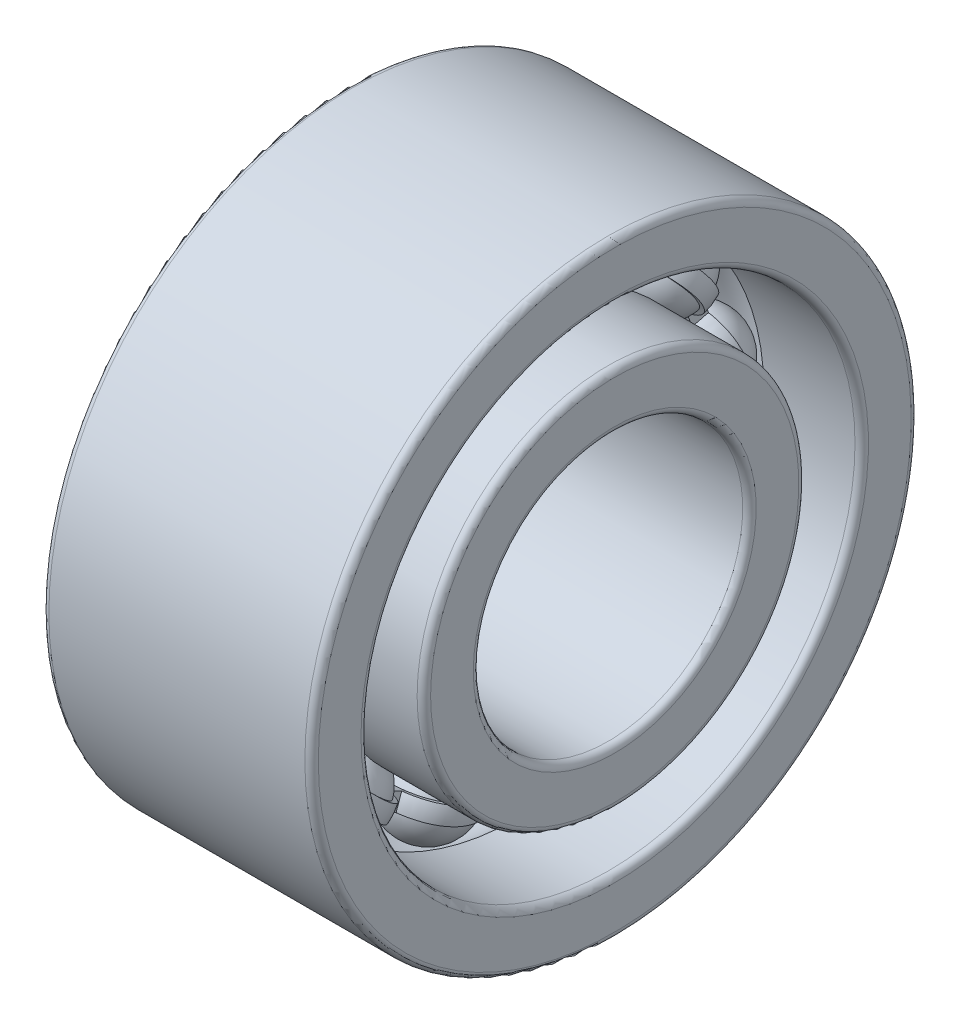
SolidWorks part; units mm, degrees
note: '?' marks a value the reader was unsure of.
material "AISI 304"
ref_plane "前视基准面" through (0, 0, 0) normal (0, 0, 1) x (1, 0, 0)
ref_plane "上视基准面" through (0, 0, 0) normal (0, 1, 0) x (1, 0, 0)
ref_plane "右视基准面" through (0, 0, 0) normal (1, 0, 0) x (0, 0, -1)
sketch "尺寸草图" plane through (0, 0, 0) normal (0, 0, 1) x (1, 0, 0)
  line L0 (-19.9271, 0) -> (19.9271, 0) construction
  line L1 (0, 21.603) -> (0, -21.603) construction
  line L2 (-1.9, 4.5) -> (1.9, 4.5)
  line L3 (2, 4.4) -> (2, 3.7667)
  line L4 (-2, 4.4) -> (-2, 3.7667)
  line L5 (-1.9, 3.6667) -> (1.9, 3.6667)
  line L6 (-3.5, 3.25) -> (3.3577, 3.25) construction
  line L7 (-1.9, 2.8333) -> (1.9, 2.8333)
  line L8 (2, 2.7333) -> (2, 2.1)
  line L9 (1.9, 2) -> (-1.9, 2)
  line L10 (-2, 2.1) -> (-2, 2.7333)
  line L11 (0, 3.25) -> (0, 3.875) construction
  circle A0 centre (0, 3.25) radius 0.625
  arc A1 (2, 3.7667) -> (1.9, 3.6667) centre (1.9, 3.7667) cw
  arc A2 (2, 2.7333) -> (1.9, 2.8333) centre (1.9, 2.7333) ccw
  arc A3 (-1.9, 2.8333) -> (-2, 2.7333) centre (-1.9, 2.7333) ccw
  arc A4 (-1.9, 3.6667) -> (-2, 3.7667) centre (-1.9, 3.7667) cw
  arc A5 (-1.9, 2) -> (-2, 2.1) centre (-1.9, 2.1) cw
  arc A6 (1.9, 2) -> (2, 2.1) centre (1.9, 2.1) ccw
  arc A7 (2, 4.4) -> (1.9, 4.5) centre (1.9, 4.4) ccw
  arc A8 (-1.9, 4.5) -> (-2, 4.4) centre (-1.9, 4.4) ccw
  point P7 (0, 0)
  point P25 (-2, 2.8333)
  point P28 (-2, 3.6667)
  point P31 (-2, 2)
  point P36 (2, 4.5)
  point P39 (-2, 4.5)
  dimension "D1" = 0.2083
  dimension "D3" = 0.1
  dimension "B" = 4
  dimension "D2" = 2
  dimension "D" = 9
  dimension "(d)" = 4
  dimension "D5" = 3.25
  dimension "D6" = 0.8333
  dimension "D7" = 0.8333
sketch "草图2" plane through (0, 0, 0) normal (0, 0, 1) x (1, 0, 0)
  line L6 (1.9, 2) -> (-1.9, 2) construction
  line L8 (-2, 4.4) -> (-2, 3.7667) construction
  line L9 (-1.9, 3.6667) -> (1.9, 3.6667) construction
  line L10 (-1.9, 4.5) -> (1.9, 4.5) construction
  line L11 (2, 4.4) -> (2, 3.7667) construction
  line L12 (2, 2.7333) -> (2, 2.1) construction
  line L13 (-1.9, 2.8333) -> (1.9, 2.8333) construction
  line L14 (1.9, 2) -> (-1.9, 2)
  line L15 (-2, 2.1) -> (-2, 2.7333) construction
  line L18 (-3.5, 0) -> (3.5, 0) construction
  line L19 (-19.9271, 0) -> (19.9271, 0) construction
  line L20 (-2, 4.4) -> (-2, 3.7667)
  line L21 (-1.9, 3.6667) -> (-0.4658, 3.6667)
  line L22 (-1.9, 4.5) -> (1.9, 4.5)
  line L23 (2, 4.4) -> (2, 3.7667)
  line L24 (2, 2.7333) -> (2, 2.1)
  line L25 (-1.9, 2.8333) -> (-0.4658, 2.8333)
  line L26 (-2, 2.1) -> (-2, 2.7333)
  line L27 (0.4658, 3.6667) -> (1.9, 3.6667)
  line L28 (0.4658, 2.8333) -> (1.9, 2.8333)
  circle A0 centre (0, 3.25) radius 0.625 construction
  arc A1 (0.4658, 3.6667) -> (-0.4658, 3.6667) centre (0, 3.25) ccw
  arc A2 (-0.4658, 2.8333) -> (0.4658, 2.8333) centre (0, 3.25) ccw
  arc A3 (-1.9, 4.5) -> (-2, 4.4) centre (-1.9, 4.4) ccw construction
  arc A4 (-2, 3.7667) -> (-1.9, 3.6667) centre (-1.9, 3.7667) ccw construction
  arc A5 (2, 4.4) -> (1.9, 4.5) centre (1.9, 4.4) ccw construction
  arc A6 (1.9, 3.6667) -> (2, 3.7667) centre (1.9, 3.7667) ccw construction
  arc A7 (2, 2.7333) -> (1.9, 2.8333) centre (1.9, 2.7333) ccw construction
  arc A8 (1.9, 2) -> (2, 2.1) centre (1.9, 2.1) ccw construction
  arc A9 (-1.9, 2.8333) -> (-2, 2.7333) centre (-1.9, 2.7333) ccw construction
  arc A10 (-2, 2.1) -> (-1.9, 2) centre (-1.9, 2.1) ccw construction
  arc A11 (-1.9, 4.5) -> (-2, 4.4) centre (-1.9, 4.4) ccw
  arc A12 (-2, 3.7667) -> (-1.9, 3.6667) centre (-1.9, 3.7667) ccw
  arc A13 (2, 4.4) -> (1.9, 4.5) centre (1.9, 4.4) ccw
  arc A14 (1.9, 3.6667) -> (2, 3.7667) centre (1.9, 3.7667) ccw
  arc A15 (2, 2.7333) -> (1.9, 2.8333) centre (1.9, 2.7333) ccw
  arc A16 (1.9, 2) -> (2, 2.1) centre (1.9, 2.1) ccw
  arc A17 (-1.9, 2.8333) -> (-2, 2.7333) centre (-1.9, 2.7333) ccw
  arc A18 (-2, 2.1) -> (-1.9, 2) centre (-1.9, 2.1) ccw
revolve "旋转1" add sketch "草图2" angle 360 about L18
sketch "草图5" plane through (0, 0, 0) normal (0, 0, 1) x (1, 0, 0)
  line L1 (-0.1875, 3.125) -> (0.1875, 3.125)
  line L2 (-0.1875, 3.125) -> (-0.1875, 3.375)
  line L3 (-0.1875, 3.375) -> (0.1875, 3.375)
  line L4 (0.1875, 3.125) -> (0.1875, 3.375)
  line L5 (-0.1875, 3.125) -> (0.1875, 3.375) construction
  line L6 (-0.1875, 3.375) -> (0.1875, 3.125) construction
  circle A0 centre (0, 3.25) radius 0.625 construction
  circle A1 centre (0, 3.25) radius 0.625 construction
  point P0 (0, 3.25)
  dimension "D1" = 0.375
  dimension "D2" = 0.25
revolve "旋转3" add sketch "草图5" angle 360 about L0
ref_axis "基准轴1" through (-3.85, 0, 0) along (1, 0, 0)?
sketch "草图3" plane through (0, 0, 0) normal (0, 0, 1) x (1, 0, 0)
  line L1 (-0.6875, 3.25) -> (0.6875, 3.25)
  circle A0 centre (0, 3.25) radius 0.625 construction
  circle A1 centre (0, 3.25) radius 0.625 construction
  arc A2 (0.6875, 3.25) -> (-0.6875, 3.25) centre (0, 3.25) ccw
  dimension "D2" = 1.375
revolve "旋转2" add sketch "草图3" angle 360 about L1
pattern_circular "阵列(圆周)5" count 13 over 360 about axis through (0, 0, 0) along (1, 0, 0) of bodies 103
sketch "草图6" plane through (0, 0, 0) normal (0, 0, 1) x (1, 0, 0)
  line L0 (-0.676, 3.375) -> (0.676, 3.375)
  line L1 (-3.5, 3.25) -> (2, 3.25) construction
  line L3 (-0.676, 3.125) -> (0.676, 3.125)
  line L4 (2, -4.4) -> (2, 4.4) construction
  arc A0 (-0.676, 3.125) -> (0.676, 3.125) centre (0, 3.25) ccw
  circle A1 centre (0, 3.25) radius 0.625 construction
  circle A2 centre (0, 3.25) radius 0.625 construction
  arc A3 (0.676, 3.375) -> (-0.676, 3.375) centre (0, 3.25) ccw
  dimension "D1" = 1.375
  dimension "D3" = 0.125
  dimension "D4" = 0.125
revolve "切除-旋转1" cut sketch "草图6" angle 360 about L0
sketch "草图7" plane through (0, 0, 0) normal (0, 0, 1) x (1, 0, 0)
  line L0 (-0.625, 3.25) -> (0.625, 3.25)
  line L1 (-2, 0) -> (2, 0) construction
  line L2 (-2, 4.4) -> (-2, -4.4) construction
  line L3 (2, -4.4) -> (2, 4.4) construction
  circle A0 centre (0, 3.25) radius 0.625 construction
  arc A1 (0.625, 3.25) -> (-0.625, 3.25) centre (0, 3.25) ccw
revolve "旋转4" add sketch "草图7" angle 360 about L0
pattern_circular "阵列(圆周)2" count 13 over 360 about axis through (0, 0, 0) along (1, 0, 0) of "旋转4"
